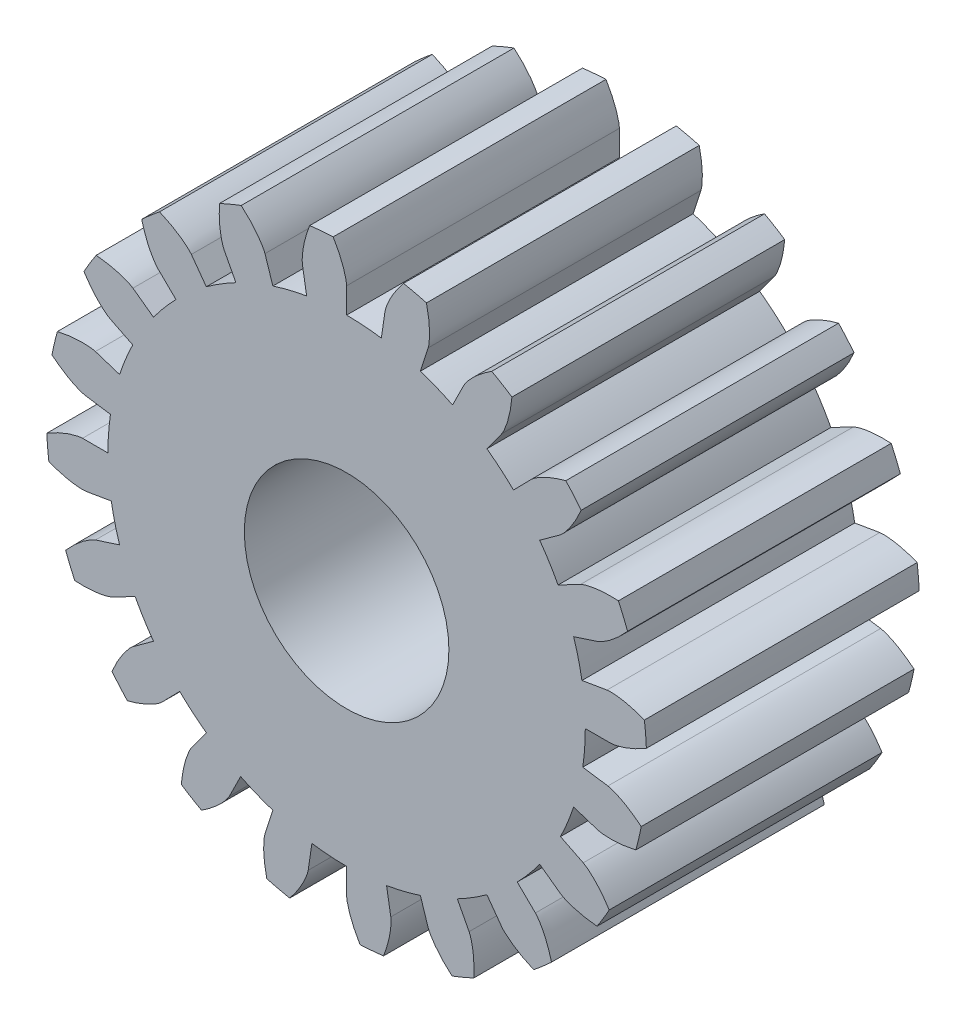
SolidWorks part; units mm, degrees
note: '?' marks a value the reader was unsure of.
ref_plane "Front" through (0, 0, 0) normal (0, 0, 1) x (1, 0, 0)
ref_plane "Top" through (0, 0, 0) normal (0, 1, 0) x (1, 0, 0)
ref_plane "Right" through (0, 0, 0) normal (1, 0, 0) x (0, 0, -1)
ref_axis "Axis1" through (0, 0, -80.9) along (0, 0, 1)?
sketch "Sketch1" plane through (0, 0, 0) normal (0, 0, 1) x (1, 0, 0)
  circle A0 centre (0, 0) radius 13.97
  dimension "D1" = 27.94
extrude "Boss-Extrude1" add sketch "Sketch1" against normal blind 12.7
sketch "Sketch2" plane through (0, 0, 0) normal (0, 0, 1) x (1, 0, 0)
  line L0 (5.5562, 0) -> (12.2955, 0)
  line L1 (0, 0) -> (7.9609, -0.5821) construction
  line L2 (5.4971, -0.8083) -> (12.1647, -1.7886)
  circle A0 centre (0, 0) radius 12.7 construction
  circle A1 centre (0, 0) radius 12.2955 construction
  circle A2 centre (0, 0) radius 11.1125 construction
  arc A3 (5.4971, -0.8083) -> (5.5562, 0) centre (0, 0) ccw
  spline S0 degree 4 poles (12.2955, 0) (12.3334, 0.0016) (12.4392, 0.0113) (12.6387, 0.0497) (12.9559, 0.1402) (13.3535, 0.2977) (13.8441, 0.5454) (14.3886, 0.8895) (14.9497, 1.3205) (15.5112, 1.8367) (16.0301, 2.3953) (16.5074, 2.9897) (16.9657, 3.6455) (17.4779, 4.4934) (18.0044, 5.5516) (18.4989, 6.8327) (18.9055, 8.3033) (19.1753, 9.8049) (19.3149, 11.3237) (19.3304, 12.8489) (19.228, 14.3702) (19.0133, 15.8804) (18.6928, 17.3701) (18.3495, 18.5622) (18.0424, 19.461) (17.8048, 20.0883) (17.6689, 20.4324) (17.5375, 20.7467) (17.455, 20.9411) (17.3421, 21.1956) (17.2479, 21.407) (17.0876, 21.7524) (16.836, 22.2709) (16.5737, 22.771) (16.3352, 23.2106) (16.1929, 23.4555) (16.1111, 23.598) knots 0 0 0 0 0 0.005604 0.015718 0.02996 0.048734 0.068727 0.096889 0.125051 0.153212 0.181374 0.209535 0.237696 0.271429 0.327752 0.384075 0.440398 0.496721 0.553044 0.609367 0.66569 0.722013 0.778336 0.834659 0.84874 0.86282 0.876901 0.890982 0.895509 0.900036 0.909091 0.931818 0.954545 0.977273 1 1 1 1 1 construction
  spline S1 degree 4 poles (12.2955, 0) (12.3334, 0.0016) (12.4392, 0.0113) (12.6387, 0.0497) (12.9559, 0.1402) (13.3535, 0.2977) (13.8441, 0.5454) (14.3886, 0.8895) (14.9497, 1.3205) (15.5112, 1.8367) (16.0301, 2.3953) (16.5074, 2.9897) (16.9657, 3.6455) (17.4779, 4.4934) (18.0044, 5.5516) (18.4989, 6.8327) (18.9055, 8.3033) (19.1753, 9.8049) (19.3149, 11.3237) (19.3304, 12.8489) (19.228, 14.3702) (19.0133, 15.8804) (18.6928, 17.3701) (18.3495, 18.5622) (18.0424, 19.461) (17.8048, 20.0883) (17.6689, 20.4324) (17.5375, 20.7467) (17.455, 20.9411) (17.3421, 21.1956) (17.3003, 21.2893) (17.2669, 21.3631) (17.2438, 21.4137) knots 0 0 0 0 0 0.005604 0.015718 0.02996 0.048734 0.068727 0.096889 0.125051 0.153212 0.181374 0.209535 0.237696 0.271429 0.327752 0.384075 0.440398 0.496721 0.553044 0.609367 0.66569 0.722013 0.778336 0.834659 0.84874 0.86282 0.876901 0.890982 0.895509 0.900036 0.909091 0.909091 0.909091 0.909091 0.909091
  spline S2 degree 4 poles (12.1647, -1.7886) (12.2019, -1.7958) (12.3053, -1.8207) (12.497, -1.8878) (12.7977, -2.0234) (13.1682, -2.2371) (13.6175, -2.5535) (14.1061, -2.9732) (14.5985, -3.4812) (15.079, -4.0736) (15.5111, -4.7017) (15.8969, -5.3593) (16.2549, -6.0747) (16.6383, -6.9882) (17.0052, -8.1117) (17.3082, -9.4511) (17.4964, -10.9652) (17.545, -12.4901) (17.4622, -14.013) (17.2556, -15.5243) (16.933, -17.0145) (16.5009, -18.4774) (15.9671, -19.9046) (15.4541, -21.034) (15.0195, -21.8786) (14.6931, -22.4647) (14.5086, -22.7854) (14.3329, -23.0772) (14.223, -23.2576) (14.0743, -23.4929) (13.9503, -23.6884) (13.7415, -24.0068) (13.4172, -24.4831) (13.0849, -24.9397) (12.7849, -25.34) (12.6085, -25.5616) (12.5069, -25.6907) knots 0 0 0 0 0 0.005604 0.015718 0.02996 0.048734 0.068727 0.096889 0.125051 0.153212 0.181374 0.209535 0.237696 0.271429 0.327752 0.384075 0.440398 0.496721 0.553044 0.609367 0.66569 0.722013 0.778336 0.834659 0.84874 0.86282 0.876901 0.890982 0.895509 0.900036 0.909091 0.931818 0.954545 0.977273 1 1 1 1 1 construction
  spline S3 degree 4 poles (12.1647, -1.7886) (12.2019, -1.7958) (12.3053, -1.8207) (12.497, -1.8878) (12.7977, -2.0234) (13.1682, -2.2371) (13.6175, -2.5535) (14.1061, -2.9732) (14.5985, -3.4812) (15.079, -4.0736) (15.5111, -4.7017) (15.8969, -5.3593) (16.2549, -6.0747) (16.6383, -6.9882) (17.0052, -8.1117) (17.3082, -9.4511) (17.4964, -10.9652) (17.545, -12.4901) (17.4622, -14.013) (17.2556, -15.5243) (16.933, -17.0145) (16.5009, -18.4774) (15.9671, -19.9046) (15.4541, -21.034) (15.0195, -21.8786) (14.6931, -22.4647) (14.5086, -22.7854) (14.3329, -23.0772) (14.223, -23.2576) (14.0743, -23.4929) (14.0193, -23.5796) (13.9755, -23.6477) (13.9452, -23.6944) knots 0 0 0 0 0 0.005604 0.015718 0.02996 0.048734 0.068727 0.096889 0.125051 0.153212 0.181374 0.209535 0.237696 0.271429 0.327752 0.384075 0.440398 0.496721 0.553044 0.609367 0.66569 0.722013 0.778336 0.834659 0.84874 0.86282 0.876901 0.890982 0.895509 0.900036 0.909091 0.909091 0.909091 0.909091 0.909091
  dimension "D1" = 25.4
  dimension "D2" = 24.591
  dimension "D3" = 22.225
  dimension "D5" = 11.1125
  dimension "D4" = 4.182
extrude "Cut-Extrude1" cut sketch "Sketch2" against normal through all and the other way through all
pattern_circular "CirPattern1" count 20 over 360 about axis through (0, 0, -12.7) along (0, 0, 1) of "Cut-Extrude1"
sketch "Sketch3" plane through (0, 0, 0) normal (0, 0, 1) x (1, 0, 0)
  circle A1 centre (0, 0) radius 11.1125 construction
  circle A2 centre (0, 0) radius 11.1125
extrude "Boss-Extrude2" add sketch "Sketch3" against normal up to surface (12.7 mm away) up to face at (0, 0, -12.7)
sketch "Sketch4" plane through (0, 0, 0) normal (0, 0, 1) x (1, 0, 0)
  circle A0 centre (0, 0) radius 12.7 construction
  circle A1 centre (0, 0) radius 12.7
surface "Pitch Circle" sketch "Sketch4"
sketch "Sketch5" plane through (0, 0, 0) normal (0, 0, 1) x (1, 0, 0)
  circle A0 centre (0, 0) radius 4.7625
  dimension "D1" = 9.525
extrude "Cut-Extrude2" cut sketch "Sketch5" against normal through all
equation "\"P\"= \"P0\"'Diametral Pitch"
equation "\"N\"= \"N0\"'Number of Teeth"
equation "\"phi\"= \"phi0\"'Pressure Angle"
equation "\"a\"= 1 / \"P\"'Addendum"
equation "\"b\"= 1.25 / \"P\"'Dedendum"
equation "\"c\"= \"b\" - \"a\"'Clearance"
equation "\"dp\"= \"N\" / \"P\"'Pitch Circle Diameter"
equation "\"db\"= \"dp\" * cos ( \"phi\" )'Base Circle Diameter"
equation "\"alpha\"= sqr ( \"dp\" ^ 2 - \"db\" ^ 2 ) / \"db\" * 180deg / pi - \"phi\""
equation "\"D1@Sketch1\"=\"dp\"+2*\"a\""
equation "\"D3@Sketch2\"=\"dp\"-2*\"b\""
equation "\"D1@Sketch2\"=\"dp\""
equation "\"D2@Sketch2\"=\"db\""
equation "\"D4@Sketch2\"=360 / ( 4 * \"N\" ) - \"alpha\""
equation "\"D5@Sketch2\"=(\"dp\"-2*\"b\")/2"
equation "\"D1@CirPattern1\"=\"N\""
